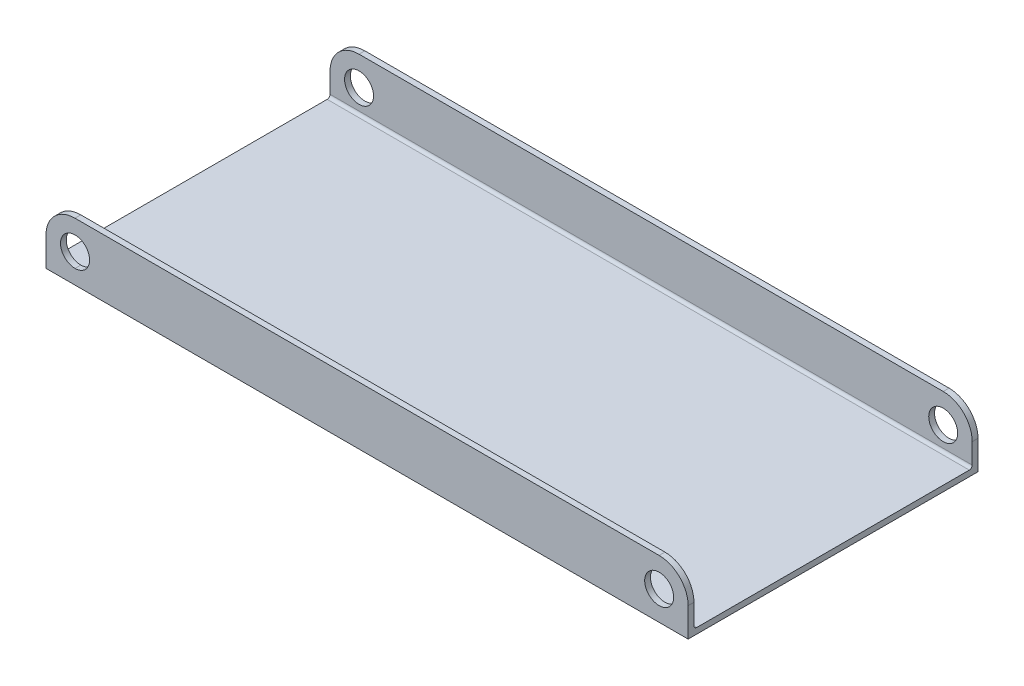
SolidWorks part; units mm, degrees
material "AISI 1020"
ref_plane "Front Plane" through (0, 0, 0) normal (0, 0, 1) x (1, 0, 0)
ref_plane "Top Plane" through (0, 0, 0) normal (0, 1, 0) x (1, 0, 0)
ref_plane "Right Plane" through (0, 0, 0) normal (1, 0, 0) x (0, 0, -1)
sketch "Sketch1" plane through (0, 0, 0) normal (0, 1, 0) x (1, 0, 0)
  line L0 (0, 31.75) -> (140.6769, 31.75) construction
  line L1 (0, 0) -> (140.6769, 0)
  line L2 (0, 0) -> (0, 63.5)
  line L3 (0, 63.5) -> (140.6769, 63.5)
  line L4 (140.6769, 0) -> (140.6769, 63.5)
  line L5 (2.8606, 0) -> (2.8606, 1.27) construction
  line L6 (0, 1.27) -> (140.6769, 1.27)
  line L7 (0, 63.5) -> (140.6769, 63.5)
  line L8 (0, 62.23) -> (140.6769, 62.23)
  dimension "D1" = 60.96
  dimension "D2" = 63.5
extrude "Boss-Extrude1" add sketch "Sketch1" along normal blind 12.7 contours L6 L2 L1 L4 region at (70.3385, 0, -0.635)
extrude "Boss-Extrude2" add sketch "Sketch1<3>" along normal blind 1.27 contours L2 L6 L4 L3 region at (70.3385, 0, -31.75)
sketch "Sketch1<3>" plane through (0, 0, 0) normal (0, 1, 0) x (1, 0, 0) same geometry as "Sketch1"
sketch "Sketch2" plane through (0, 0, 0) normal (0, 0, 1) x (1, 0, 0)
  line L0 (0, 6.35) -> (6.3736, 6.35) construction
  line L1 (0, 12.7) -> (0, 0) construction
  line L2 (140.6769, 6.35) -> (146.05, 6.35) construction
  line L3 (140.6769, 12.7) -> (140.6769, 0) construction
  circle A0 centre (6.3736, 6.35) radius 3.175
  circle A1 centre (146.05, 6.35) radius 3.175
extrude "Cut-Extrude1" cut sketch "Sketch2" against normal blind 508
extrude "Boss-Extrude3" add sketch "Sketch1<5>" along normal blind 12.7 contours L2 L8 L4 L3 region at (70.3385, 0, -62.865)
sketch "Sketch1<5>" plane through (0, 0, 0) normal (0, 1, 0) x (1, 0, 0) same geometry as "Sketch1"
sketch "Sketch3" plane through (0, 0, -63.5) normal (0, 0, -1) x (-1, 0, 0)
  line L0 (0, 6.35) -> (-6.35, 6.35) construction
  line L1 (0, 12.7) -> (0, 0) construction
  line L2 (-140.6769, 6.35) -> (-146.05, 6.35) construction
  line L3 (-140.6769, 12.7) -> (-140.6769, 0) construction
  line L4 (-140.6769, 6.35) -> (-134.3269, 6.35) construction
  circle A0 centre (-6.35, 6.35) radius 3.175
  circle A1 centre (-146.05, 6.35) radius 3.175
  circle A2 centre (-134.3269, 6.35) radius 3.175
extrude "Cut-Extrude2" cut sketch "Sketch3" against normal blind 12.7
fillet "Fillet1" radius 6.35 4 edges at (0, 12.7, -0.635) (140.6769, 12.7, -0.635) (140.6769, 12.7, -62.865) (0, 12.7, -62.865)
fillet "Fillet2" radius 0.635 2 edges at (70.3385, 1.27, -1.27) (70.3385, 1.27, -62.23)
extrude "Cut-Extrude3" cut sketch "Sketch3<2>" against normal through all
sketch "Sketch3<2>" plane through (0, 0, -63.5) normal (0, 0, -1) x (-1, 0, 0) same geometry as "Sketch3"
equation "\"A\"= 20.5"
equation "\"B\"= 6.5"
equation "\"C\"= 36deg"
